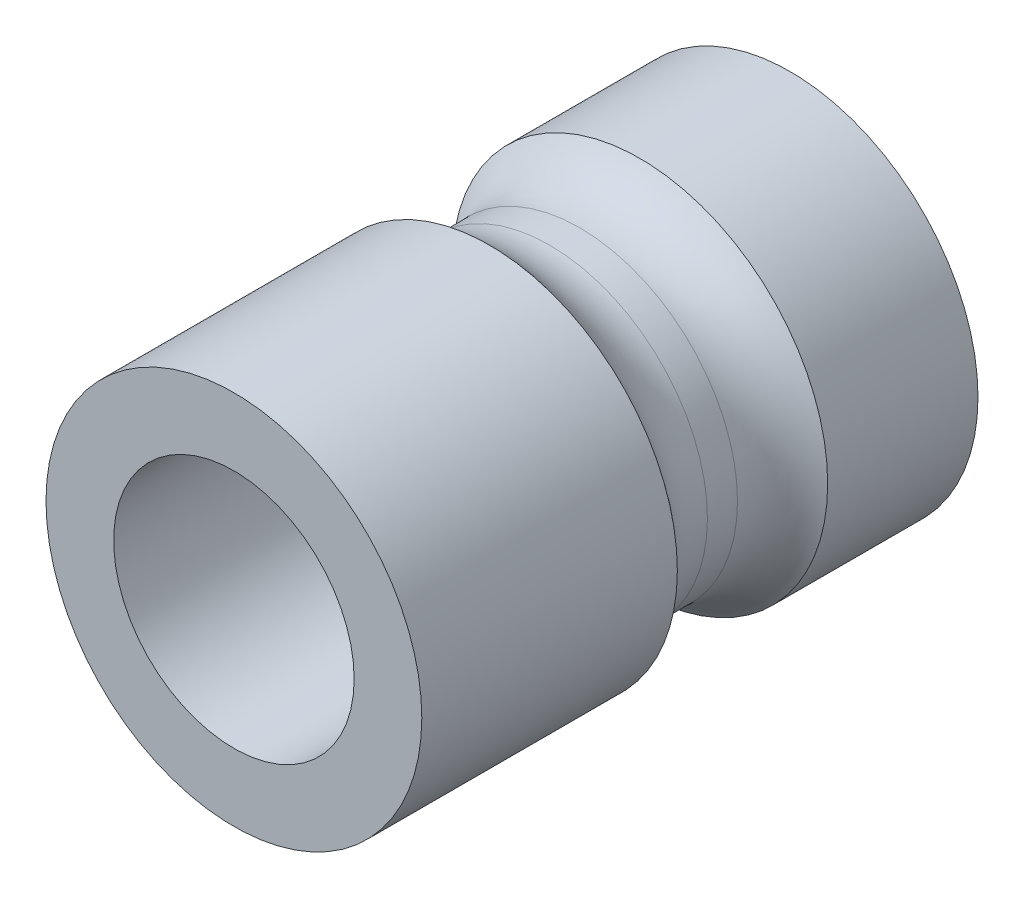
SolidWorks part; units mm, degrees
ref_plane "Спереди" through (0, 0, 0) normal (0, 0, 1) x (1, 0, 0)
ref_plane "Сверху" through (0, 0, 0) normal (0, 1, 0) x (1, 0, 0)
ref_plane "Справа" through (0, 0, 0) normal (1, 0, 0) x (0, 0, -1)
sketch "Эскиз1" plane through (0, 0, 0) normal (0, 0, 1) x (1, 0, 0)
  circle A0 centre (0, 0) radius 2.5
extrude "Бобышка-Вытянуть1" add sketch "Эскиз1" along normal blind 2
sketch "Эскиз2" plane through (0, 0, 2) normal (0, 0, 1) x (1, 0, 0)
  circle A0 centre (0, 0) radius 2.1
extrude "Бобышка-Вытянуть2" add sketch "Эскиз2" along normal blind 2
sketch "Эскиз3" plane through (0, 0, 4) normal (0, 0, 1) x (1, 0, 0)
  circle A0 centre (0, 0) radius 2.5
extrude "Бобышка-Вытянуть3" add sketch "Эскиз3" along normal blind 3.4
sketch "Эскиз4" plane through (0, 0, 7.4) normal (0, 0, 1) x (1, 0, 0)
  circle A0 centre (0, 0) radius 1.6
extrude "Вырез-Вытянуть1" cut sketch "Эскиз4" against normal through all
fillet "Скругление1" radius 1 2 edges at (2.1, 0, 4) (2.1, 0, 2)
